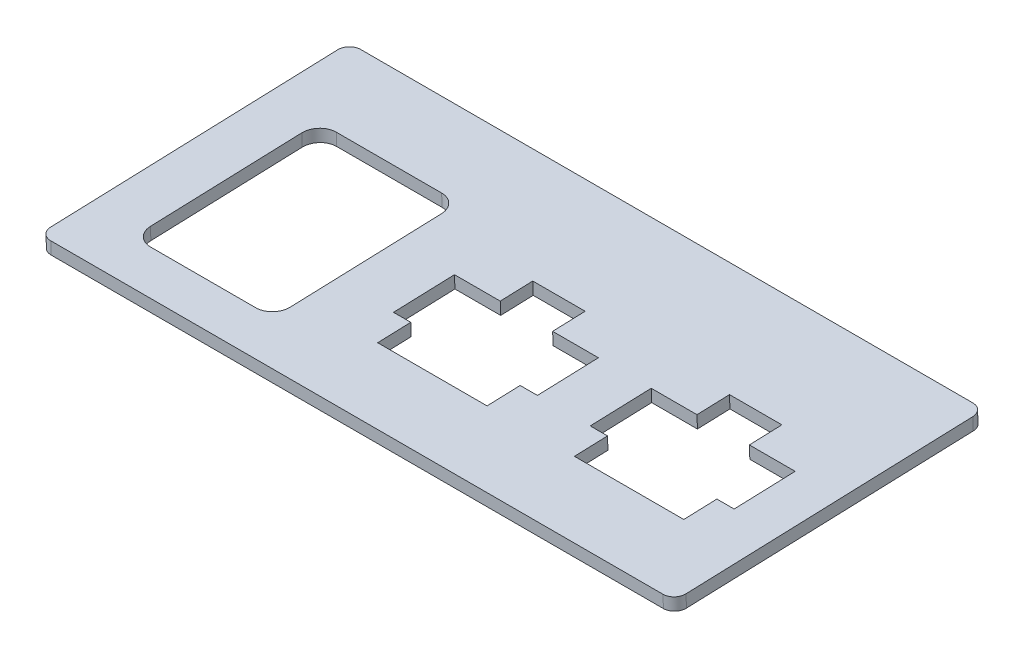
SolidWorks part; units mm, degrees
ref_plane "Front Plane" through (0, 0, 0) normal (0, 0, 1) x (1, 0, 0)
ref_plane "Top Plane" through (0, 0, 0) normal (0, 1, 0) x (1, 0, 0)
ref_plane "Right Plane" through (0, 0, 0) normal (1, 0, 0) x (0, 0, -1)
sketch "Sketch1" plane through (0, -71.9872, -2.5138) normal (0, 0.9994, 0.0349) x (1, 0, 0)
  line L0 (-56.175, 49.6404) -> (56.175, 49.6404) construction
  line L1 (-52.175, -2.9116) -> (-56.175, -2.9116) construction
  line L8 (-55.175, -4.2116) -> (55.175, -4.2116)
  line L9 (55.175, -4.2116) -> (55.175, 49.6404)
  line L10 (55.175, 49.6404) -> (-55.175, 49.6404)
  line L11 (-55.175, 49.6404) -> (-55.175, -4.2116)
  dimension "D4" = 0
  dimension "D1" = 1.3
  dimension "D2" = 3.0034
  dimension "D3" = 3.0034
extrude "Boss-Extrude1" add sketch "Sketch1" along normal blind 2.2
sketch "Sketch2" plane through (0, -71.9872, -2.5138) normal (0, -0.9994, -0.0349) x (1, 0, 0)
  line L0 (-4.05, -24.7624) -> (-4.05, -30.4124)
  line L1 (-43.325, -3.2624) -> (-25.025, -3.2624)
  line L2 (-46.325, -6.2624) -> (-46.325, -32.5624)
  line L3 (-43.325, -35.5624) -> (-25.025, -35.5624)
  line L4 (-22.025, -6.2624) -> (-22.025, -32.5624)
  line L5 (-12, -14.1624) -> (-9, -14.1624)
  line L6 (-12, -14.1624) -> (-12, -24.7624)
  line L7 (-12, -24.7624) -> (-4.05, -24.7624)
  line L8 (13, -14.1624) -> (13, -24.7624)
  line L9 (-9, -8.4124) -> (10, -8.4124)
  line L10 (-9, -8.4124) -> (-9, -14.1624)
  line L11 (-4.05, -30.4124) -> (5.05, -30.4124)
  line L12 (10, -8.4124) -> (10, -14.1624)
  line L13 (10, -14.1624) -> (13, -14.1624)
  line L14 (5.05, -24.7624) -> (5.05, -30.4124)
  line L15 (5.05, -24.7624) -> (13, -24.7624)
  line L16 (-13, -5.9124) -> (14, -32.9124) construction
  line L17 (-13, -5.9124) -> (14, -5.9124) construction
  line L18 (-13, -5.9124) -> (-13, -32.9124) construction
  line L19 (-13, -32.9124) -> (14, -32.9124) construction
  line L20 (14, -5.9124) -> (14, -32.9124) construction
  line L21 (17.5875, 3.7502) -> (17.5875, -36.664) construction
  line L22 (47.175, -19.4624) -> (22.175, -19.4624) construction
  line L23 (34.675, -8.4124) -> (34.675, -30.4124) construction
  line L24 (21.175, -5.9124) -> (21.175, -32.9124) construction
  line L25 (48.175, -32.9124) -> (21.175, -32.9124) construction
  line L26 (48.175, -5.9124) -> (48.175, -32.9124) construction
  line L27 (48.175, -5.9124) -> (21.175, -5.9124) construction
  line L28 (-48.175, -19.4124) -> (-46.325, -19.4124) construction
  line L29 (-48.175, -1.4124) -> (-20.175, -1.4124) construction
  line L30 (-48.175, -1.4124) -> (-48.175, -37.4124) construction
  line L31 (-48.175, -37.4124) -> (-20.175, -37.4124) construction
  line L32 (-20.175, -1.4124) -> (-20.175, -37.4124) construction
  line L33 (-34.175, -3.2624) -> (-34.175, -1.4124) construction
  line L34 (0.5, -8.4124) -> (0.5, -30.4124) construction
  line L35 (-12, -19.4624) -> (13, -19.4624) construction
  line L36 (48.175, -5.9124) -> (21.175, -32.9124) construction
  line L37 (30.125, -24.7624) -> (22.175, -24.7624)
  line L38 (30.125, -24.7624) -> (30.125, -30.4124)
  line L39 (25.175, -14.1624) -> (22.175, -14.1624)
  line L40 (25.175, -8.4124) -> (25.175, -14.1624)
  line L41 (39.225, -30.4124) -> (30.125, -30.4124)
  line L42 (44.175, -8.4124) -> (44.175, -14.1624)
  line L43 (44.175, -8.4124) -> (25.175, -8.4124)
  line L44 (22.175, -14.1624) -> (22.175, -24.7624)
  line L45 (47.175, -24.7624) -> (39.225, -24.7624)
  line L46 (47.175, -14.1624) -> (47.175, -24.7624)
  line L47 (47.175, -14.1624) -> (44.175, -14.1624)
  line L48 (39.225, -24.7624) -> (39.225, -30.4124)
  line L49 (21.175, -19.4124) -> (14, -19.4124) construction
  line L51 (48.175, -19.4124) -> (52.175, -19.4124) construction
  line L52 (55.175, 4.2116) -> (55.175, -49.6404) construction
  line L53 (-46.7565, -41.6404) -> (46.7565, -41.6404) construction
  line L54 (-13, -19.4124) -> (-20.175, -19.4124) construction
  line L55 (-34.175, -1.4124) -> (-34.175, 2.8156) construction
  line L56 (-34.175, -37.4124) -> (-34.175, -41.6404) construction
  line L57 (-55.175, -49.6404) -> (-55.175, 4.2116) construction
  line L58 (-48.175, -19.4124) -> (-52.175, -19.4124) construction
  line L59 (-53.075, 2.8156) -> (53.075, 2.8156) construction
  arc A0 (-46.325, -32.5624) -> (-43.325, -35.5624) centre (-43.325, -32.5624) ccw
  arc A1 (-25.025, -35.5624) -> (-22.025, -32.5624) centre (-25.025, -32.5624) ccw
  arc A2 (-25.025, -3.2624) -> (-22.025, -6.2624) centre (-25.025, -6.2624) cw
  arc A3 (-43.325, -3.2624) -> (-46.325, -6.2624) centre (-43.325, -6.2624) ccw
  point P28 (0.5, -19.4124)
  point P63 (34.675, -19.4124)
  dimension "D1" = 3
  dimension "D2" = 32.3
  dimension "D3" = 24.3
  dimension "D4" = 28
  dimension "D5" = 36
  dimension "D6" = 25
  dimension "D7" = 22
  dimension "D8" = 10.6
  dimension "D9" = 19
  dimension "D10" = 9.1
  dimension "D11" = 5.75
  dimension "D12" = 27
  dimension "D13" = 27
  dimension "D14" = 4
  dimension "D15" = 3
  dimension "D16" = 3
extrude "Cut-Extrude1" cut sketch "Sketch2" against normal up to next
fillet "Fillet1" radius 2 4 edges at (-55.175, -71.0348, 1.7336) (55.175, -71.0348, 1.7336) (55.175, -69.1554, -52.0856) (-55.175, -69.1554, -52.0856)
